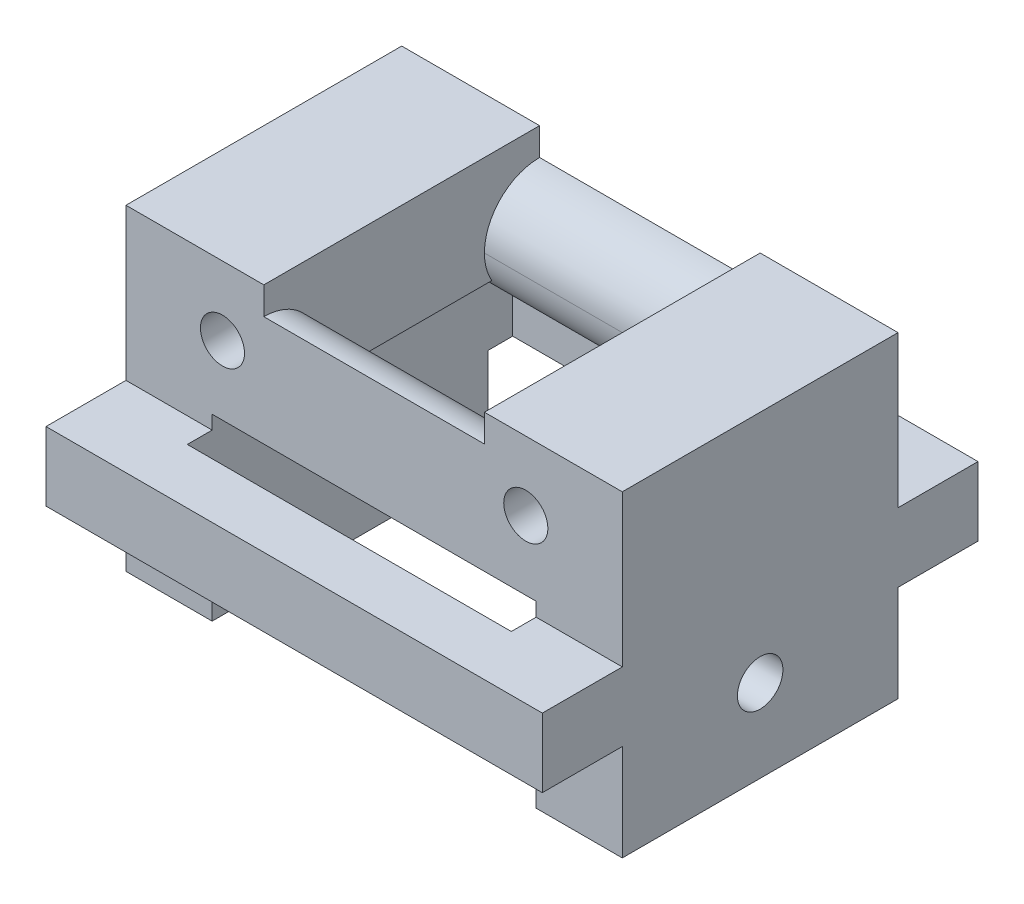
SolidWorks part; units mm, degrees
ref_plane "Front" through (0, 0, 0) normal (0, 0, 1) x (1, 0, 0)
ref_plane "Top" through (0, 0, 0) normal (0, 1, 0) x (1, 0, 0)
ref_plane "Right" through (0, 0, 0) normal (1, 0, 0) x (0, 0, -1)
sketch "Sketch1" plane through (0, 0, 0) normal (0, 1, 0) x (1, 0, 0)
  line L1 (0, 0) -> (36, 0)
  line L2 (0, 0) -> (0, -20)
  line L3 (0, -20) -> (36, -20)
  line L4 (36, 0) -> (36, -20)
  dimension "D1" = 36
  dimension "D2" = 20
extrude "Boss-Extrude1" add sketch "Sketch1" along normal blind 15
sketch "Sketch2" plane through (0, 0, 0) normal (0, -1, 0) x (-1, 0, 0)
  line L0 (0, -20) -> (-36, -20) construction
  line L1 (-6.25, -20) -> (-29.75, -20)
  line L2 (-6.25, -20) -> (-6.25, 0)
  line L3 (-6.25, 0) -> (-29.75, 0)
  line L4 (-29.75, -20) -> (-29.75, 0)
  line L5 (-36, 0) -> (0, 0) construction
  dimension "D1" = 6.25
  dimension "D2" = 6.25
extrude "Cut-Extrude1" cut sketch "Sketch2" against normal blind 13
sketch "Sketch3" plane through (0, 0, 0) normal (-1, 0, 0) x (0, 0, 1)
  line L0 (0, 0) -> (20, 0) construction
  line L1 (20, 15) -> (20, 0) construction
  circle A0 centre (10, 6) radius 1.65
  dimension "D1" = 3.3
  dimension "D2" = 6
  dimension "D3" = 10
extrude "Cut-Extrude2" cut sketch "Sketch3" against normal through all
sketch "Sketch4" plane through (0, 15, 0) normal (0, 1, 0) x (1, 0, 0)
  line L0 (36, -20) -> (36, 0) construction
  line L1 (28, -4) -> (8, -4)
  line L2 (28, -4) -> (28, -16)
  line L3 (28, -16) -> (8, -16)
  line L4 (8, -4) -> (8, -16)
  line L5 (36, 0) -> (0, 0) construction
  line L6 (0, 0) -> (0, -20) construction
  line L7 (0, -20) -> (36, -20) construction
  dimension "D1" = 8
  dimension "D2" = 4
  dimension "D3" = 8
  dimension "D4" = 4
extrude "Cut-Extrude3" cut sketch "Sketch4" against normal through all
sketch "Sketch5" plane through (0, 15, 0) normal (0, 1, 0) x (1, 0, 0)
  line L0 (0, 0) -> (0, -20) construction
  line L1 (36, 0) -> (26, 0)
  line L2 (36, 0) -> (36, -20)
  line L3 (36, -20) -> (26, -20)
  line L4 (26, 0) -> (26, -20)
  line L5 (10, 0) -> (0, 0)
  line L6 (10, 0) -> (10, -20)
  line L7 (10, -20) -> (0, -20)
  line L8 (0, 0) -> (0, -20)
  line L11 (36, 0) -> (0, 0) construction
  line L13 (0, -20) -> (36, -20) construction
  point P14 (0, 0)
  dimension "D1" = 20
  dimension "D2" = 20
  dimension "D3" = 0
  dimension "D4" = 10
  dimension "D5" = 10
  dimension "D6" = 0
  dimension "D7" = 26
  dimension "D8" = 0
extrude "Boss-Extrude2" add sketch "Sketch5" along normal blind 8
sketch "Sketch6" plane through (0, 0, 0) normal (0, 0, -1) x (-1, 0, 0)
  line L0 (-36, 23) -> (-36, 0) construction
  line L1 (-36, 23) -> (-26, 23) construction
  circle A0 centre (-29, 18) radius 1.6
  circle A1 centre (-7, 18) radius 1.6
  dimension "D1" = 3.2
  dimension "D2" = 7
  dimension "D3" = 5
  dimension "D4" = 2
extrude "Cut-Extrude4" cut sketch "Sketch6" against normal through all
sketch "Sketch7" plane through (0, 15, 0) normal (0, 1, 0) x (1, 0, 0)
  line L1 (10, -20) -> (26, -20)
  line L2 (10, -20) -> (10, -16)
  line L3 (10, -16) -> (26, -16)
  line L4 (26, -20) -> (26, -16)
  line L5 (26, 0) -> (10, 0)
  line L6 (26, 0) -> (26, -4)
  line L7 (26, -4) -> (10, -4)
  line L8 (10, 0) -> (10, -4)
extrude "Boss-Extrude3" add sketch "Sketch7" along normal blind 6
fillet "Fillet1" radius 4 2 edges at (18, 13, 16) (18, 13, 4)
fillet "Fillet2" radius 4 2 edges at (8, 15, 10) (28, 15, 10)
fillet "Fillet5" radius 4 2 edges at (18, 21, 16) (18, 21, 4)
sketch "Sketch8" plane through (0, 0, 0) normal (-1, 0, 0) x (0, 0, 1)
  line L0 (20, 23) -> (20, 0) construction
  line L1 (20, 12) -> (25.8, 12)
  line L2 (20, 12) -> (20, 7)
  line L3 (20, 7) -> (25.8, 7)
  line L4 (25.8, 12) -> (25.8, 7)
  line L5 (0, 23) -> (0, 0) construction
  line L6 (0, 12) -> (-5.8, 12)
  line L7 (0, 12) -> (0, 7)
  line L8 (0, 7) -> (-5.8, 7)
  line L9 (-5.8, 12) -> (-5.8, 7)
  dimension "D1" = 5
  dimension "D2" = 5
  dimension "D3" = 5.8
  dimension "D4" = 5.8
  dimension "D5" = 11
  dimension "D6" = 11
extrude "Boss-Extrude4" add sketch "Sketch8" against normal blind 36
sketch "Sketch9" plane through (0, 7, 0) normal (0, -1, 0) x (-1, 0, 0)
  line L1 (-6.25, 0) -> (-29.75, 0)
  line L2 (-6.25, 0) -> (-6.25, 1.8)
  line L3 (-6.25, 1.8) -> (-29.75, 1.8)
  line L4 (-29.75, 0) -> (-29.75, 1.8)
  line L5 (-6.25, -20) -> (-29.75, -20)
  line L6 (-6.25, -20) -> (-6.25, -21.8)
  line L7 (-6.25, -21.8) -> (-29.75, -21.8)
  line L8 (-29.75, -20) -> (-29.75, -21.8)
  dimension "D1" = 1.8
  dimension "D2" = 1.8
  dimension "D3" = 0
  dimension "D4" = 0
extrude "Cut-Extrude5" cut sketch "Sketch9" against normal through all
